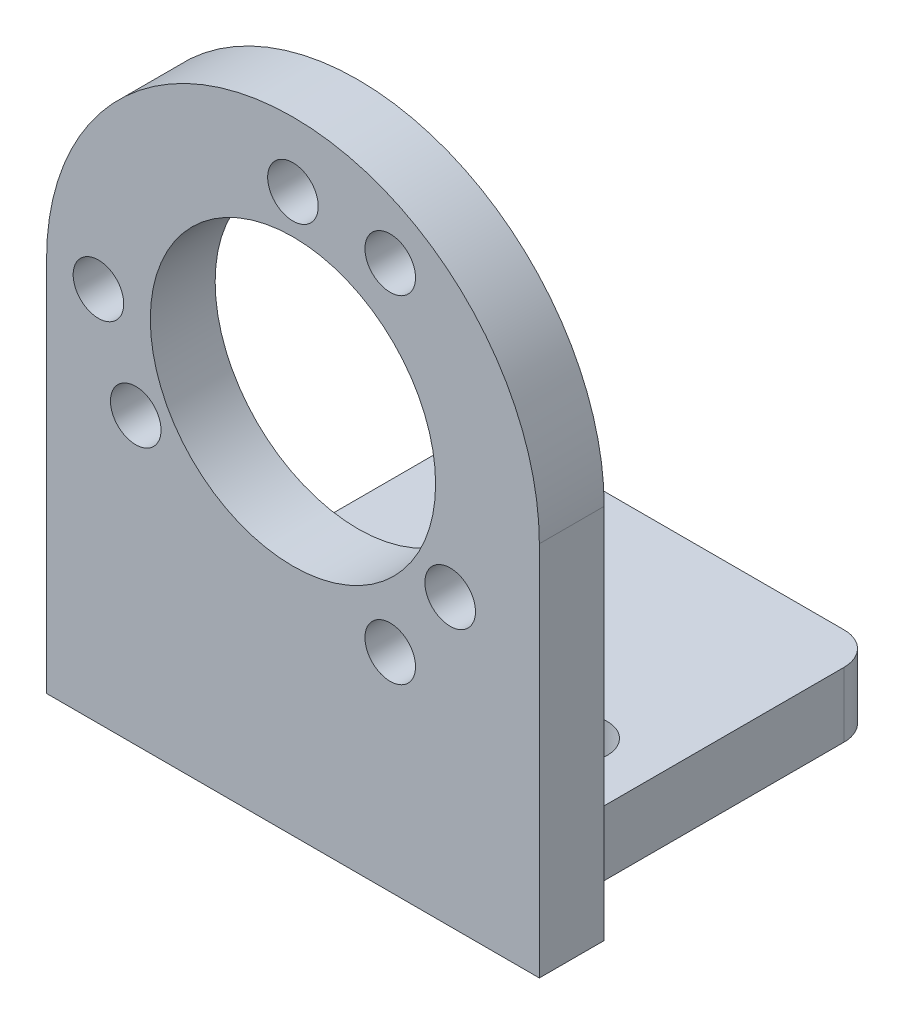
SolidWorks part; units mm, degrees
material "ABS"
ref_plane "Front Plane" through (0, 0, 0) normal (0, 0, 1) x (1, 0, 0)
ref_plane "Top Plane" through (0, 0, 0) normal (0, 1, 0) x (1, 0, 0)
ref_plane "Right Plane" through (0, 0, 0) normal (1, 0, 0) x (0, 0, -1)
sketch "Sketch1" plane through (0, 0, 0) normal (0, 0, 1) x (1, 0, 0)
  line L0 (-19, 0) -> (-19, -29)
  line L1 (-19, -29) -> (19, -29)
  line L2 (19, -29) -> (19, 0)
  circle A0 centre (0, 0) radius 19
  circle A1 centre (0, 0) radius 11
  dimension "D1" = 38
  dimension "D2" = 10
  dimension "D3" = 22
extrude "Boss-Extrude1" add sketch "Sketch1" along normal blind 5 contours A0 A1 | A0 L0 L1 L2 region at (0, -21.3225, 0) region at (0, 18.4626, 0)
sketch "Sketch2" plane through (0, 0, 0) normal (0, 0, -1) x (-1, 0, 0)
  line L1 (-15, -29) -> (15, -29)
  line L2 (-15, -29) -> (-15, -24)
  line L3 (-15, -24) -> (15, -24)
  line L4 (15, -29) -> (15, -24)
  line L5 (19, -29) -> (-19, -29) construction
  point P8 (0, -24)
  dimension "D1" = 5
  dimension "D2" = 30
extrude "Boss-Extrude2" add sketch "Sketch2" along normal blind 25
hole_wizard "M3 Clearance Hole1" positions "Sketch3" profile "Sketch4" hole size "M3" standard "ANSI Metric" end condition up to next
sketch "Sketch3" plane through (0, 0, 5) normal (0, 0, 1) x (1, 0, 0)
  line L0 (0, 0) -> (0, 14) construction
  line L2 (0, 0) -> (7.5, 12.9904) construction
  circle A0 centre (0, 0) radius 14 construction
  circle A1 centre (0, 0) radius 15 construction
  point P5 (0, 14)
  point P14 (12.1244, -7)
  point P15 (-12.1244, -7)
  point P19 (7.5, 12.9904)
  point P32 (7.5, -12.9904)
  point P33 (-15, 0)
  dimension "D1" = 28
  dimension "D2" = 3
  dimension "D3" = 30
  dimension "D4" = 30
sketch "Sketch4" plane through (-15, 0, 5) normal (1, 0, 0) x (0, -1, 0)
  line L0 (0, 0) -> (0, 5)
  line L1 (0, 5) -> (1.95, 5)
  line L2 (1.95, 5) -> (1.95, 0)
  line L5 (1.95, 0) -> (0, 0)
  line L11 (0, -6.35) -> (0, 107.95) construction
  dimension "Thru Hole Dia." = 3.9
  dimension "Thru Hole Depth" = 5
hole_wizard "M4 Clearance Hole1" positions "Sketch5" profile "Sketch6" hole size "M4" standard "ANSI Metric" end condition up to next
sketch "Sketch5" plane through (0, -24, 0) normal (0, 1, 0) x (1, 0, 0)
  line L0 (9.5, 7.5) -> (-9.5, 7.5) construction
  line L1 (-15, 25) -> (15, 25) construction
  point P1 (-9.5, 7.5)
  point P20 (9.5, 7.5)
  point P24 (0, 7.5)
  dimension "D1" = 19
  dimension "D2" = 17.5
sketch "Sketch6" plane through (-9.5, -24, -7.5) normal (1, 0, 0) x (0, 0, 1)
  line L0 (0, 0) -> (0, 5)
  line L1 (0, 5) -> (2.25, 5)
  line L2 (2.25, 5) -> (2.25, 0)
  line L5 (2.25, 0) -> (0, 0)
  line L11 (0, -6.35) -> (0, 107.95) construction
  dimension "Thru Hole Dia." = 4.5
  dimension "Thru Hole Depth" = 5
fillet "Fillet1" radius 2.5 5 edges at (-15, -26.5, -25) (15, -26.5, -25) (0, -24, 0) (-15, -26.5, 0) (15, -26.5, 0)
